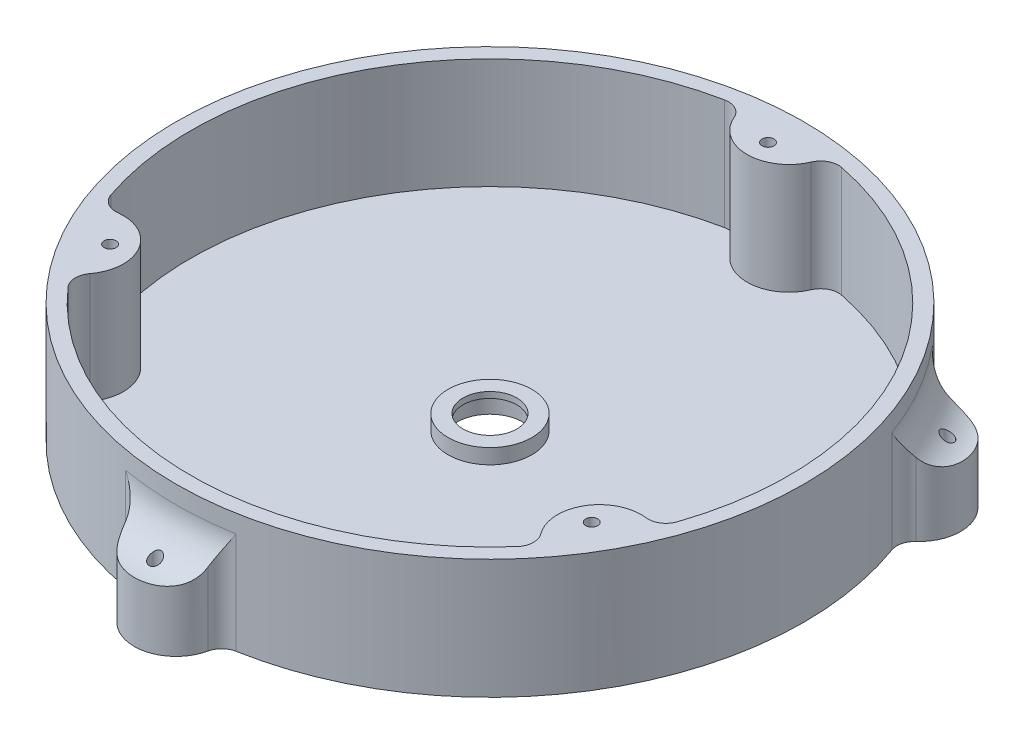
SolidWorks part; units mm, degrees
material "PE High Density"
ref_plane "Front Plane" through (0, 0, 0) normal (0, 0, 1) x (1, 0, 0)
ref_plane "Top Plane" through (0, 0, 0) normal (0, 1, 0) x (1, 0, 0)
ref_plane "Right Plane" through (0, 0, 0) normal (1, 0, 0) x (0, 0, -1)
sketch "Sketch1" plane through (0, 0, 0) normal (0, 1, 0) x (1, 0, 0)
  circle A0 centre (0, 0) radius 100
  circle A1 centre (0, 0) radius 105
  circle A2 centre (0, 0) radius 6
  circle A3 centre (0, 0) radius 11
  circle A4 centre (0, 0) radius 14
  circle A5 centre (0, 0) radius 9
  dimension "D1" = 200
  dimension "D2" = 5
  dimension "D3" = 12
  dimension "D4" = 3
  dimension "D5" = 22
  dimension "D6" = 18
extrude "Boss-Extrude1" add sketch "Sketch1" along normal blind 40 contours A1 A0 region at (-102.0302, 0, 0)
extrude "Boss-Extrude2" add sketch "Sketch1<2>" along normal blind 3 contours A0 | A4 A3 region at (-97.1716, 0, 0) region at (-13.604, 0, 0)
sketch "Sketch1<2>" plane through (0, 0, 0) normal (0, 1, 0) x (1, 0, 0) same geometry as "Sketch1"
extrude "Boss-Extrude8" add sketch "Sketch1<4>" along normal blind 5 from surface contours A4 A3 region at (-13.604, 0, 0) starting at face at (0, 3, 100)
sketch "Sketch1<4>" plane through (0, 0, 0) normal (0, 1, 0) x (1, 0, 0) same geometry as "Sketch1"
sketch "Sketch2" plane through (0, 3, 0) normal (0, 1, 0) x (1, 0, 0)
  line L0 (0, 0) -> (0, 86) construction
  line L1 (0, 0) -> (79.3623, 0) construction
  line L4 (-96.9948, 56) -> (0, 0) construction
  line L5 (-96.9948, 56) -> (-103.057, 59.5) construction
  line L7 (0, 93) -> (0, 86) construction
  circle A1 centre (0, 0) radius 100 construction
  circle A2 centre (0, 0) radius 100 construction
  arc A4 (-13.9657, 99.02) -> (13.9657, 99.02) centre (0, 100) ccw
  arc A5 (-13.9657, 99.02) -> (13.9657, 99.02) centre (0, 0) cw
  circle A6 centre (0, 93) radius 2
  arc A7 (-97.1088, 39.936) -> (-83.1399, 64.1307) centre (0, 0) cw
  circle A8 centre (0, 0) radius 105 construction
  arc A9 (-97.1088, 39.936) -> (-83.1399, 64.1307) centre (-90.9327, 52.5) cw
  circle A10 centre (-96.9948, 56) radius 2
  circle M8 centre (0, 0) radius 100
  dimension "D1" = 4
  dimension "D2" = 7
  dimension "D5" = 14
  dimension "D3" = 60
extrude "Boss-Extrude3" add sketch "Sketch2" along normal up to surface (37 mm away) from surface contours A4 A6 M8 region at (0, 3, -99.6876) up to face at (0, 40, 100) starting at face at (0, 0, 105)
extrude "Boss-Extrude9" add sketch "Sketch2<6>" along normal blind 20 from surface contours A9 A7 A10 region at (-102.7595, 3, -59.3282) starting at face at (0, 0, 105)
sketch "Sketch2<6>" plane through (0, 3, 0) normal (0, 1, 0) x (1, 0, 0) same geometry as "Sketch2"
fillet "Fillet1" radius 6 4 edges at (13.9657, 21.5, -99.02) (-13.9657, 21.5, -99.02) (-97.1088, 10, -39.936) (-83.1399, 10, -64.1307)
pattern_circular "CirPattern1" count 3 over 360 about axis through (0, 40, 0) along (0, -1, 0) of "Boss-Extrude3", "Fillet1", "Boss-Extrude9"
fillet "Fillet2" radius 14 3 edges at (90.9327, 20, -52.5) (0, 20, 105) (-90.9327, 20, -52.5)
extrude "Boss-Extrude10" add sketch "Sketch1<5>" against normal blind 2 from surface contours A3 A5 region at (-10.6889, 0, 0) starting at face at (0, 8, 14)
sketch "Sketch1<5>" plane through (0, 0, 0) normal (0, 1, 0) x (1, 0, 0) same geometry as "Sketch1"
